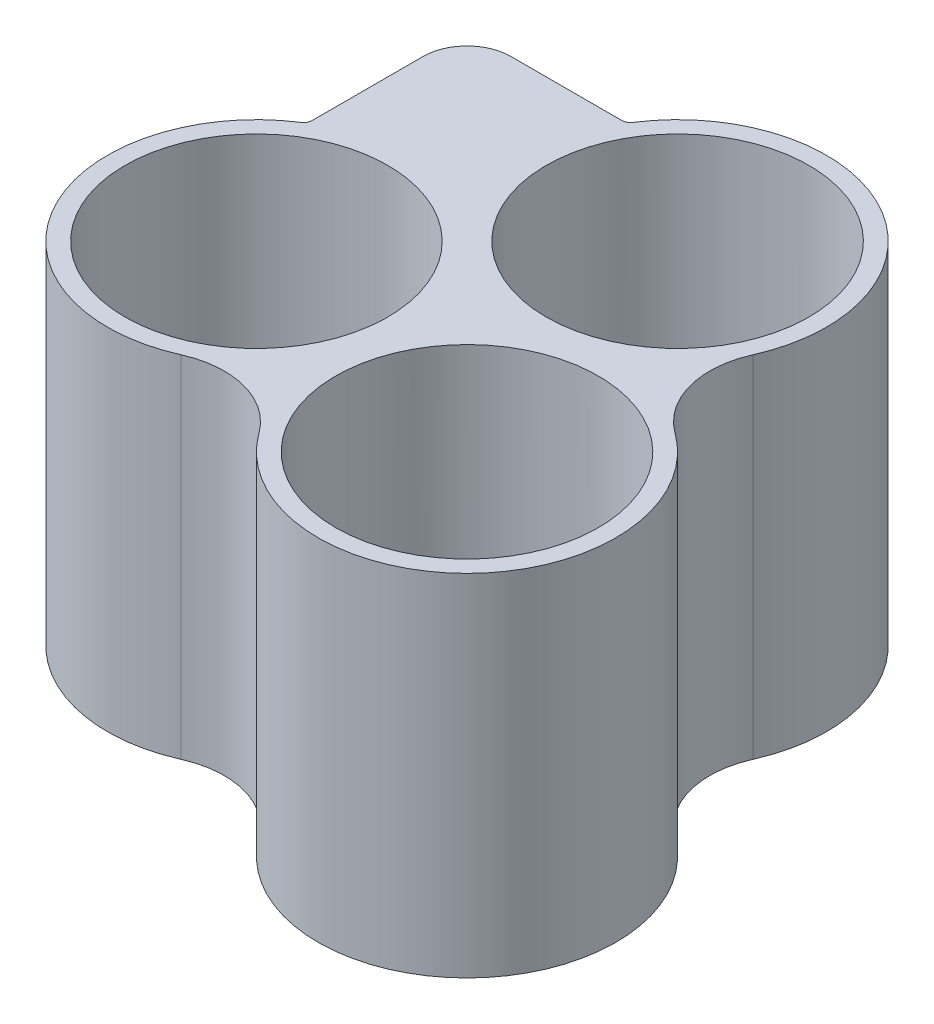
SolidWorks part; units mm, degrees
ref_plane "Front Plane" through (0, 0, 0) normal (0, 0, 1) x (1, 0, 0)
ref_plane "Top Plane" through (0, 0, 0) normal (0, 1, 0) x (1, 0, 0)
ref_plane "Right Plane" through (0, 0, 0) normal (1, 0, 0) x (0, 0, -1)
sketch "Sketch1" plane through (0, 0, 0) normal (0, 1, 0) x (1, 0, 0)
  line L1 (-15, -15) -> (15, -15)
  line L2 (-15, -15) -> (-15, 15)
  line L3 (-15, 15) -> (15, 15)
  line L4 (15, -15) -> (15, 15)
  line L5 (-15, -15) -> (15, 15) construction
  line L6 (-15, 15) -> (15, -15) construction
  point P0 (0, 0)
  dimension "D1" = 30
extrude "Boss-Extrude1" add sketch "Sketch1" along normal blind 80
sketch "Sketch2" plane through (0, 80, 0) normal (0, 1, 0) x (1, 0, 0)
  line L0 (-15, -15) -> (15, -15) construction
  line L1 (15, -15) -> (15, 15) construction
  circle A0 centre (9, -9) radius 6
  dimension "D1" = 12
extrude "Boss-Extrude2" add sketch "Sketch2" along normal blind 22
sketch "Sketch3" plane through (0, 80, 0) normal (0, 1, 0) x (1, 0, 0)
  line L2 (9, -15) -> (15, -15)
  line L4 (15, -15) -> (15, -9)
  circle A1 centre (9, -9) radius 6
  arc A4 (9, -15) -> (15, -9) centre (9, -9) ccw
  dimension "D1" = 0
extrude "Cut-Extrude1" cut sketch "Sketch3" against normal through all
sketch "Sketch4" plane through (0, 80, 0) normal (0, 1, 0) x (1, 0, 0)
  line L1 (-8.25, 11.25) -> (-1.75, 11.25) construction
  line L2 (-8.25, 11.25) -> (-8.25, 8.25)
  line L6 (-1.75, 1.75) -> (-11.25, 1.75)
  line L8 (-8.25, 8.25) -> (-11.25, 8.25)
  line L9 (-11.25, 1.75) -> (-11.25, 8.25) construction
  line L10 (-1.75, 11.25) -> (-1.75, 1.75)
  line L11 (-11.25, -1.25) -> (1.25, -1.25)
  line L12 (1.25, -1.25) -> (1.25, 11.25)
  line L13 (1.25, 11.25) -> (-1.75, 11.25) construction
  line L14 (-11.25, 1.75) -> (-11.25, -1.25) construction
  line L15 (-11.25, 8.25) -> (-11.25, 11.25) construction
  line L16 (-11.25, 11.25) -> (-8.25, 11.25) construction
  line L17 (1.25, 11.25) -> (1.25, 15)
  line L18 (15, 15) -> (-15, 15) construction
  line L19 (1.25, 15) -> (-1.75, 15)
  line L20 (-1.75, 15) -> (-1.75, 11.25)
  line L21 (-8.25, 11.25) -> (-8.25, 15)
  line L22 (-8.25, 15) -> (-11.25, 15)
  line L23 (-11.25, 15) -> (-11.25, 11.25)
  line L24 (-11.25, 11.25) -> (-15, 11.25)
  line L25 (-15, 15) -> (-15, -15) construction
  line L26 (-15, 11.25) -> (-15, 8.25)
  line L27 (-15, 8.25) -> (-11.25, 8.25)
  line L28 (-11.25, 1.75) -> (-15, 1.75)
  line L29 (-15, 1.75) -> (-15, -1.25)
  line L30 (-15, -1.25) -> (-11.25, -1.25)
  dimension "D1" = 6.5
  dimension "D2" = 3
  dimension "D3" = 3.75
extrude "Boss-Extrude3" add sketch "Sketch4" along normal blind 100
sketch "Sketch6" plane through (0, 0, 0) normal (0, -1, 0) x (1, 0, 0)
  line L1 (15, -15) -> (7, -15)
  line L2 (15, -15) -> (15, -105.5)
  line L3 (15, -105.5) -> (13, -105.5)
  line L4 (7, -15) -> (7, -99.5)
  arc A1 (7, -99.5) -> (13, -105.5) centre (7, -105.5) ccw
  dimension "D3" = 12
  dimension "D1" = 90.5
  dimension "D2" = 8
extrude "Boss-Extrude5" add sketch "Sketch6" against normal blind 2
sketch "Sketch7" plane through (0, 2, 0) normal (0, 1, 0) x (1, 0, 0)
  line L0 (7, 109.5) -> (7, 111.5) construction
  line L1 (9, 111.1569) -> (9, 108.9641)
  line L2 (5, 111.1569) -> (5, 108.9641)
  line L3 (7, 101.5) -> (7, 99.5) construction
  line L4 (15, 105.5) -> (13, 105.5)
  line L5 (15, 105.5) -> (15, 15)
  line L6 (15, 15) -> (7, 15)
  line L7 (7, 15) -> (7, 99.5) construction
  line L8 (15, 15) -> (1.25, 15) construction
  line L9 (7, 15) -> (7, 99.5)
  arc A0 (5, 111.1569) -> (7, 99.5) centre (7, 105.5) ccw
  arc A1 (13, 105.5) -> (7, 99.5) centre (7, 105.5) ccw construction
  arc A2 (5, 108.9641) -> (9, 108.9641) centre (7, 105.5) ccw
  arc A3 (13, 105.5) -> (9, 111.1569) centre (7, 105.5) ccw
  dimension "D1" = 2
  dimension "D2" = 2
extrude "Boss-Extrude6" add sketch "Sketch7" along normal offset from surface (23 mm away) 25 up to face at (3.75, 0, -38.4375)
sketch "Sketch9" plane through (0, 0, 0) normal (0, -1, 0) x (1, 0, 0)
  line L0 (15, -15) -> (7, -15) construction
  line L1 (-15, 15) -> (-132.175, 15) construction
  line L2 (-15, 15) -> (-15, 7)
  line L3 (-15, 7) -> (-126.175, 7) construction
  line L4 (-132.175, 15) -> (-132.175, 13.1746) construction
  line L5 (-136.05, 7) -> (-136.175, 7) construction
  line L6 (-128.175, 7) -> (-126.175, 7) construction
  line L7 (-126.175, 9) -> (-128.856, 9) construction
  line L8 (7, -109.5) -> (7, -111.5) construction
  line L9 (9, -111.1569) -> (5, -111.1569) construction
  line L10 (-126.175, 5) -> (-128.856, 5) construction
  line L11 (-126.175, 9) -> (-126.175, 5) construction
  line L12 (-128.7978, 8.9) -> (-126.3, 8.9)
  line L13 (-128.7978, 5.1) -> (-126.175, 5.1) construction
  line L14 (-126.175, 5.1) -> (-126.175, 7) construction
  line L15 (-126.175, 8.9) -> (-126.3, 8.9) construction
  line L16 (-132.05, 15) -> (-132.05, 13.1733)
  line L17 (-132.05, 14.0867) -> (-132.175, 14.0873) construction
  line L18 (-132.05, 15) -> (-15, 15)
  line L19 (-126.175, 5.1) -> (-126.175, 7) construction
  line L20 (-15, 7) -> (-126.175, 7)
  line L21 (-126.4838, 5.1) -> (-128.7978, 5.1)
  circle A0 centre (-132.175, 7) radius 4 construction
  arc A1 (9, -108.9641) -> (5, -108.9641) centre (7, -105.5) ccw construction
  arc A2 (-128.7978, 8.9) -> (-128.7978, 5.1) centre (-132.175, 7) ccw
  arc A4 (-126.3, 8.9) -> (-132.175, 13.1746) centre (-132.175, 7) ccw construction
  arc A6 (-126.3, 8.9) -> (-132.05, 13.1733) centre (-132.175, 7) ccw
  arc A7 (-126.4838, 5.1) -> (-126.175, 7) centre (-132.175, 7) ccw
  arc A8 (7, -99.5) -> (5, -111.1569) centre (7, -105.5) ccw construction
  dimension "D1" = 117.175
  dimension "D2" = 0.125
  dimension "D3" = 1.9
extrude "Boss-Extrude7" add sketch "Sketch9" against normal blind 25
fillet "Fillet1" radius 2 1 edges at (-126.175, 12.5, 7)
sketch "Sketch11" plane through (0, 0, 0) normal (0, -1, 0) x (1, 0, 0)
  line L0 (-126.3, 8.9) -> (-126.425, 8.9) construction
  line L2 (-126.3, 8.9) -> (-128.7978, 8.9) construction
  line L3 (-136.05, 7) -> (-136.175, 7) construction
  circle A0 centre (-132.175, 7) radius 6.0558
  arc A5 (-128.7978, 8.9) -> (-128.7978, 5.1) centre (-132.175, 7) ccw construction
extrude "Cut-Extrude2" cut sketch "Sketch11" against normal offset from surface (2.125 mm away) 0.125 up to face at (7, 2, -108.2802) offset beyond the face yes
sketch "Sketch12" plane through (-15, 0, 0) normal (-1, 0, 0) x (0, 0, 1)
  line L1 (-15, 77) -> (-1.75, 77)
  line L2 (-15, 77) -> (-15, 68.5)
  line L3 (-15, 68.5) -> (-1.75, 68.5)
  line L4 (-1.75, 77) -> (-1.75, 68.5)
  line L6 (-15, 80) -> (-15, 0) construction
  line L7 (-15, 80) -> (-1.75, 80) construction
  line L9 (-1.75, 180) -> (-1.75, 80) construction
  dimension "D1" = 8.5
  dimension "D2" = 3
extrude "Cut-Extrude4" cut sketch "Sketch12" against normal up to surface (13.25 mm away) up to face at (-1.75, 130, -8.375)
sketch "Sketch14" plane through (0, 0, 15) normal (0, 0, 1) x (1, 0, 0)
  line L0 (15, 0) -> (-136.05, 0) construction
  line L1 (-136.05, 25) -> (-136.05, 2.125) construction
  line L2 (-132.05, 0) -> (9, 0) construction
sketch "Sketch15" plane through (0, 80, 0) normal (0, 1, 0) x (1, 0, 0)
  line L4 (-11.25, 11.25) -> (-11.25, 15)
  line L5 (-11.25, 15) -> (-15, 15)
  line L6 (-15, 15) -> (-15, 11.25)
  line L7 (-15, 11.25) -> (-11.25, 11.25)
  line L8 (-11.25, 11.25) -> (-11.25, 15)
  line L9 (-11.25, 15) -> (-15, 15)
  line L10 (-15, 15) -> (-15, 11.25)
  line L11 (-15, 11.25) -> (-11.25, 11.25)
  dimension "D1" = 0
extrude "Cut-Extrude5" cut sketch "Sketch15" against normal up to next
fillet "Fillet2" radius 1 5 edges at (1.25, 130, -15) (-11.25, 128.5, -15) (-11.25, 128.5, -11.25) (-15, 128.5, -11.25) (-15, 130, 1.25)
sketch "Sketch16" plane through (0, 80, 0) normal (0, 1, 0) x (1, 0, 0)
  circle A0 centre (9, -9) radius 6
  circle A1 centre (9, -9) radius 6 construction
extrude "Cut-Extrude7" cut sketch "Sketch16" along normal up to next
sketch "Sketch17" plane through (0, 180, 0) normal (0, 1, 0) x (1, 0, 0)
  line L0 (18.7916, -9.75) -> (18.7916, -11.75) construction
  line L1 (1.25, 5.25) -> (3.7916, 5.25) construction
  line L2 (1.25, -1.25) -> (1.25, 14) construction
  line L3 (-5.25, -3.7916) -> (-5.25, -1.25) construction
  line L4 (-14, -1.25) -> (1.25, -1.25) construction
  line L6 (-5.25, -1.25) -> (1.25, -1.25) construction
  line L7 (1.25, -1.25) -> (1.25, 5.25) construction
  line L8 (-14, -1.25) -> (-14, -4.2164)
  line L9 (1.25, 14) -> (4.2164, 14)
  line L10 (-14, -1.25) -> (1.25, -1.25)
  line L11 (1.25, -1.25) -> (1.25, 14)
  circle A0 centre (18.7916, 5.25) radius 15
  circle A1 centre (-5.25, -18.7916) radius 15
  arc A2 (20.5619, -11.6576) -> (4.2164, 14) centre (18.7916, 5.25) ccw
  arc A3 (-14, -4.2164) -> (11.6576, -20.5619) centre (-5.25, -18.7916) ccw
  arc A4 (11.6576, -20.5619) -> (20.5619, -11.6576) centre (21.6032, -21.6032) cw
  dimension "D1" = 30
  dimension "D3" = 10
  dimension "D2" = 2
  dimension "D4" = 6.5
extrude "Boss-Extrude8" add sketch "Sketch17" against normal blind 40
fillet "Fillet3" radius 1 4 edges at (4.2164, 160, -14) (1.25, 160, -14) (-14, 160, 1.25) (-14, 160, 4.2164)
sketch "Sketch18" plane through (0, 140, 0) normal (0, -1, 0) x (1, 0, 0)
  circle A0 centre (-5.25, 18.7916) radius 15 construction
  circle A1 centre (-5.25, 18.7916) radius 15
  circle A2 centre (-5.25, 18.7916) radius 7.5
  dimension "D1" = 15
extrude "Boss-Extrude9" add sketch "Sketch18" against normal blind 2
sketch "Sketch19" plane through (0, 140, 0) normal (0, -1, 0) x (1, 0, 0)
  line L0 (-5.25, 26.2916) -> (-5.25, 11.2916) construction
  circle A0 centre (-5.25, 18.7916) radius 7.5 construction
ref_plane "Plane1" through (-5.25, 0, 0) normal (-1, 0, 0) x (0, 0, -1)
sketch "Sketch21" plane through (-5.25, 0, 0) normal (-1, 0, 0) x (0, 0, -1)
  line L0 (-11.2916, -142) -> (-3.7916, -154.5)
  line L1 (-26.2916, -142) -> (-11.2916, -142) construction
  line L2 (-3.7916, -154.5) -> (-3.7916, -142)
  line L3 (-33.7916, -142) -> (-3.7916, -142) construction
  line L4 (-3.7916, -142) -> (-11.2916, -142)
  line L5 (-18.7916, -1065) -> (-18.7916, 48935) construction
  line L6 (-26.2916, -140) -> (-11.2916, -140) construction
  point P14 (-18.7916, -140)
  dimension "D1" = 12.5
revolve "Revolve1" add sketch "Sketch21" angle 360 about L5
ref_plane "Plane2" through (0, 0, 0) normal (0.7071, 0, -0.7071) x (-0.7071, 0, -0.7071)
mirror "Mirror1" about plane through (0, 0, 0) normal (0.7071, 0, -0.7071) of "Revolve1", "Boss-Extrude9"
sketch "Sketch22" plane through (0, 140, 0) normal (0, -1, 0) x (1, 0, 0)
  circle A0 centre (0, 0) radius 209.0164
extrude "Cut-Extrude8" cut sketch "Sketch22" along normal through all
sketch "Sketch23" plane through (0, 180, 0) normal (0, 1, 0) x (1, 0, 0)
  line L1 (-26.7546, 5.072) -> (-4.6842, 5.072)
  line L2 (-26.7546, 5.072) -> (-26.7546, 21.2842)
  line L3 (-26.7546, 21.2842) -> (-4.6842, 21.2842)
  line L4 (-4.6842, 5.072) -> (-4.6842, 21.2842)
extrude "Cut-Extrude9" cut sketch "Sketch23" against normal through all
sketch "Sketch24" plane through (0, 180, 0) normal (0, 1, 0) x (1, 0, 0)
  line L0 (-1.75, 1.75) -> (0, 0) construction
  line L1 (0, 0) -> (39.6123, -39.6123) construction
  line L2 (-5.25, -18.7916) -> (18.7916, 5.25) construction
  line L3 (18.7916, 5.25) -> (27.5915, -27.5915) construction
  line L4 (27.5915, -27.5915) -> (-5.25, -18.7916) construction
  line L5 (-20.25, -18.7916) -> (-22.25, -18.7916) construction
  line L6 (42.5915, -27.5915) -> (44.5915, -27.5915) construction
  circle A0 centre (27.5915, -27.5915) radius 15
  circle A1 centre (18.7916, 5.25) radius 15 construction
  circle A2 centre (18.7916, 5.25) radius 15 construction
  arc A3 (13.8342, -37.5784) -> (37.5784, -13.8342) centre (27.5915, -27.5915) ccw
  circle A4 centre (-5.25, -18.7916) radius 15 construction
  arc A5 (-14.4583, -4.5015) -> (11.6576, -20.5619) centre (-5.25, -18.7916) ccw construction
  arc A6 (13.8342, -37.5784) -> (1.6707, -34.3192) centre (5.7417, -43.453) ccw
  arc A7 (37.5784, -13.8342) -> (34.3192, -1.6707) centre (43.453, -5.7417) cw
  arc A8 (20.5619, -11.6576) -> (11.6576, -20.5619) centre (21.6032, -21.6032) ccw construction
  arc A9 (20.5619, -11.6576) -> (4.5015, 14.4583) centre (18.7916, 5.25) ccw construction
  arc A10 (20.5619, -11.6576) -> (34.3192, -1.6707) centre (18.7916, 5.25) ccw
  arc A11 (20.5619, -11.6576) -> (11.6576, -20.5619) centre (21.6032, -21.6032) ccw
  arc A12 (1.6707, -34.3192) -> (11.6576, -20.5619) centre (-5.25, -18.7916) ccw
extrude "Boss-Extrude10" add sketch "Sketch24" against normal up to surface (40 mm away) up to face at (-2.677, 140, -2.677)
sketch "Sketch25" plane through (0, 140, 0) normal (0, -1, 0) x (1, 0, 0)
  circle A0 centre (27.5915, 27.5915) radius 15 construction
  circle A1 centre (27.5915, 27.5915) radius 15
  circle A2 centre (27.5915, 27.5915) radius 7.5
  circle A3 centre (-5.25, 18.7916) radius 7.5 construction
extrude "Boss-Extrude11" add sketch "Sketch25" against normal blind 2
ref_plane "Plane3" through (0, 0, 0) normal (0.7071, 0, -0.7071) x (-0.7071, 0, -0.7071)
sketch "Sketch26" plane through (0, 0, 0) normal (0.7071, 0, -0.7071) x (-0.7071, 0, -0.7071)
  line L0 (-39.0202, 126.9954) -> (-39.0202, 195.0175) construction
  line L2 (-24.0202, 142) -> (-24.0202, 154.5)
  line L3 (-24.0202, 154.5) -> (-31.5202, 142)
  line L4 (-31.5202, 142) -> (-24.0202, 142)
  line L5 (-24.0202, 142) -> (-54.0202, 142) construction
  line L7 (-24.0202, 142) -> (-24.0202, 180) construction
  line L8 (-31.5202, 142) -> (-46.5202, 142) construction
  dimension "D1" = 12.5
revolve "Revolve2" add sketch "Sketch26" angle 360 about L0
sketch "Sketch27" plane through (0, 180, 0) normal (0, 1, 0) x (1, 0, 0)
  line L0 (2.25, 14) -> (2.25, -2.25) construction
  line L1 (2.25, -2.25) -> (-14, -2.25) construction
  line L2 (2.25, -2.25) -> (2.25, 72.75)
  line L3 (2.25, 72.75) -> (-1.75, 72.75)
  line L4 (-1.75, 72.75) -> (-1.75, 1.75)
  line L5 (-1.75, 15) -> (-1.75, 1.75) construction
  line L6 (-1.75, 1.75) -> (-72.75, 1.75)
  line L7 (-72.75, 1.75) -> (-72.75, -2.25)
  line L8 (-72.75, -2.25) -> (2.25, -2.25)
  line L9 (-1.75, 1.75) -> (-15, 1.75) construction
  line L10 (3.6609, 14) -> (1.9821, 14) construction
  line L11 (-14, -1.9821) -> (-14, -3.6609) construction
  dimension "D1" = 4
  dimension "D2" = 75
extrude "Boss-Extrude12" add sketch "Sketch27" against normal up to surface (40 mm away) up to face at (0.8594, 140, 0.8594)
sketch "Sketch29" plane through (0, 0, 2.25) normal (0, 0, 1) x (1, 0, 0)
  line L0 (-72.75, 140) -> (-14, 140) construction
  line L1 (-14, 140) -> (-14, 180) construction
  line L2 (-72.75, 160) -> (-8.9096, 160) construction
  line L3 (-72.75, 140) -> (-72.75, 180) construction
  circle A0 centre (-24, 144) radius 2
  circle A1 centre (-24, 176) radius 2
  circle A2 centre (-68.75, 144) radius 2
  circle A3 centre (-68.75, 176) radius 2
  dimension "D1" = 4
  dimension "D2" = 4
  dimension "D3" = 10
  dimension "D4" = 4
extrude "Cut-Extrude10" cut sketch "Sketch29" against normal through all
sketch "Sketch30" plane through (0, 0, -1.75) normal (0, 0, -1) x (-1, 0, 0)
  line L0 (17.16, 148) -> (26.52, 148) construction
  line L1 (32.57, 148) -> (41.93, 148) construction
  line L2 (47.98, 148) -> (57.34, 148) construction
  line L3 (72.75, 140) -> (1.75, 140) construction
  line L4 (72.75, 160) -> (1.75, 160) construction
  line L5 (11.11, 148) -> (1.75, 148) construction
  line L6 (1.75, 180) -> (1.75, 140) construction
  line L7 (63.39, 148) -> (72.75, 148) construction
  line L8 (72.75, 140) -> (72.75, 180) construction
  line L9 (63.39, 172) -> (72.75, 172) construction
  line L10 (11.11, 172) -> (1.75, 172) construction
  line L11 (47.98, 172) -> (57.34, 172) construction
  line L12 (32.57, 172) -> (41.93, 172) construction
  line L13 (17.16, 172) -> (26.52, 172) construction
  circle A0 centre (14.135, 148) radius 3.025
  circle A1 centre (29.545, 148) radius 3.025
  circle A2 centre (44.955, 148) radius 3.025
  circle A3 centre (60.365, 148) radius 3.025
  circle A4 centre (60.365, 172) radius 3.025
  circle A5 centre (44.955, 172) radius 3.025
  circle A6 centre (29.545, 172) radius 3.025
  circle A7 centre (14.135, 172) radius 3.025
  dimension "D1" = 6.05
  dimension "D2" = 8
extrude "Cut-Extrude11" cut sketch "Sketch30" against normal blind 2.1
mirror "Mirror2" about plane through (0, 0, 0) normal (0.7071, 0, -0.7071) of "Cut-Extrude11", "Cut-Extrude10"
sketch "Sketch31" plane through (0, 180, 0) normal (0, 1, 0) x (1, 0, 0)
  line L0 (2.25, 14) -> (2.25, 72.75) construction
  line L1 (-77.75, 77.75) -> (2.25, 77.75)
  line L2 (-77.75, 77.75) -> (-77.75, -2.25)
  line L3 (-77.75, -2.25) -> (2.25, -2.25)
  line L4 (2.25, 77.75) -> (2.25, -2.25)
  line L5 (-72.75, -2.25) -> (-14, -2.25) construction
  dimension "D1" = 80
extrude "Cut-Extrude12" cut sketch "Sketch31" against normal through all both and the other way through all
sketch "Sketch32" plane through (0, 180, 0) normal (0, 1, 0) x (1, 0, 0)
  line L1 (-14, -2.25) -> (2.25, -2.25)
  line L2 (-14, -2.25) -> (-14, 9)
  line L3 (-9, 14) -> (2.25, 14)
  line L4 (2.25, -2.25) -> (2.25, 14)
  arc A0 (-14, 9) -> (-9, 14) centre (-9, 9) cw
  dimension "D1" = 5
extrude "Boss-Extrude13" add sketch "Sketch32" against normal offset from surface (190 mm away) 150 up to face at (5.7965, 140, 5.7965) offset beyond the face yes
sketch "Sketch33" plane through (0, 0, 2.25) normal (0, 0, 1) x (1, 0, 0)
  line L0 (-22.25, 140) -> (1.6707, 140) construction
  line L1 (-58.8107, 140) -> (17.082, 140)
  line L2 (-58.8107, 140) -> (-58.8107, -10.8319)
  line L3 (-58.8107, -10.8319) -> (17.082, -10.8319)
  line L4 (17.082, 140) -> (17.082, -10.8319)
extrude "Cut-Extrude13" cut sketch "Sketch33" against normal through all both
sketch "Sketch36" plane through (0, 140, 0) normal (0, -1, 0) x (1, 0, 0)
  line L0 (3.6609, -14) -> (-9, -14) construction
  line L5 (-14, -14) -> (2.25, -14) construction
  line L6 (-14, -14) -> (-14, 2.25) construction
  line L7 (-14, 2.25) -> (2.25, 2.25) construction
  line L8 (2.25, -14) -> (2.25, 2.25) construction
  line L9 (-14, -9) -> (-14, 3.6609) construction
  circle A0 centre (-5.875, -5.875) radius 5
  point P12 (-5.875, 2.25)
  point P13 (2.25, -5.875)
  dimension "D1" = 10
  dimension "D2" = 16.25
extrude "Cut-Extrude14" cut sketch "Sketch36" against normal blind 15
